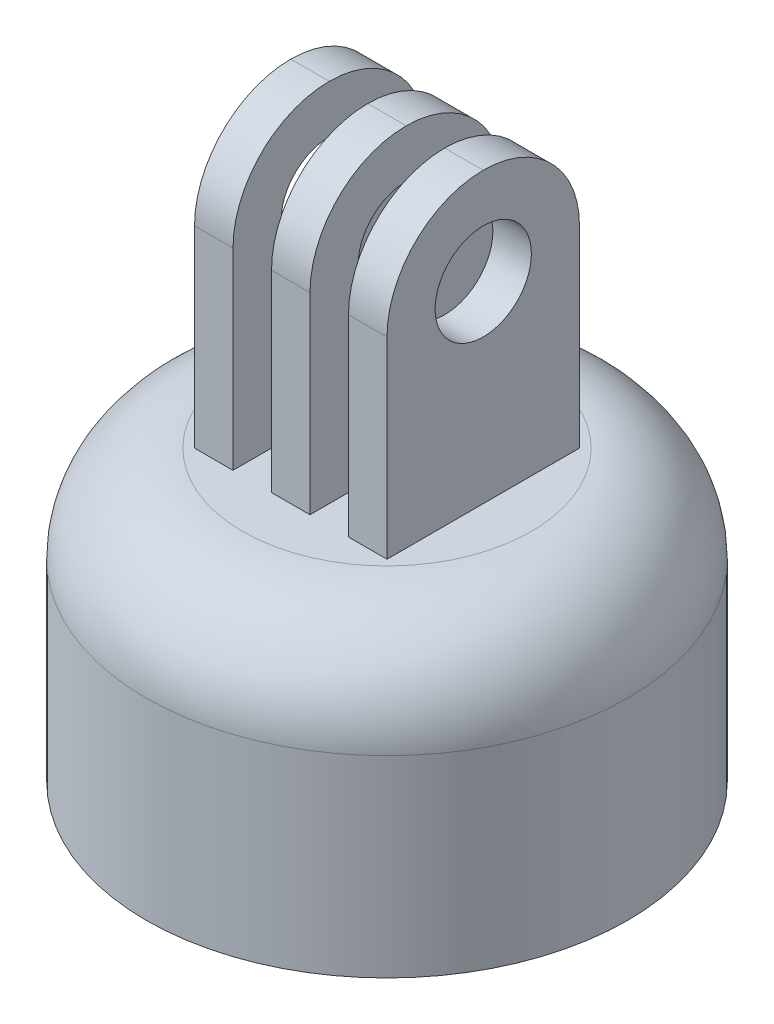
SolidWorks part; units mm, degrees
ref_plane "Front Plane" through (0, 0, 0) normal (0, 0, 1) x (1, 0, 0)
ref_plane "Top Plane" through (0, 0, 0) normal (0, 1, 0) x (1, 0, 0)
ref_plane "Right Plane" through (0, 0, 0) normal (1, 0, 0) x (0, 0, -1)
sketch "Sketch1" plane through (0, 0, 0) normal (0, 1, 0) x (1, 0, 0)
  circle A0 centre (0, 0) radius 10.5
  circle A1 centre (0, 0) radius 12.5
  dimension "D1" = 25
  dimension "D2" = 21
extrude "Boss-Extrude1" add sketch "Sketch1" along normal blind 10
sketch "Sketch2" plane through (0, 10, 0) normal (0, 1, 0) x (1, 0, 0)
  circle A1 centre (0, 0) radius 12.5
  circle A2 centre (0, 0) radius 12.5
  dimension "D1" = 0
extrude "Boss-Extrude2" add sketch "Sketch2" along normal blind 5
sketch "Sketch3" plane through (0, 15, 0) normal (0, 1, 0) x (1, 0, 0)
  line L0 (5, -5) -> (3, -5)
  line L1 (1, -5) -> (-1, -5)
  line L2 (1, -5) -> (1, 5)
  line L3 (1, 5) -> (-1, 5)
  line L4 (-1, -5) -> (-1, 5)
  line L5 (1, -5) -> (-1, 5) construction
  line L6 (1, 5) -> (-1, -5) construction
  line L7 (5, -5) -> (5, 5)
  line L8 (5, 5) -> (3, 5)
  line L9 (3, -5) -> (3, 5)
  line L10 (5, -5) -> (3, 5) construction
  line L11 (5, 5) -> (3, -5) construction
  line L12 (-3, -5) -> (-5, -5)
  line L13 (-3, -5) -> (-3, 5)
  line L14 (-3, 5) -> (-5, 5)
  line L15 (-5, -5) -> (-5, 5)
  line L16 (-3, -5) -> (-5, 5) construction
  line L17 (-3, 5) -> (-5, -5) construction
  point P0 (0, 0)
  point P7 (4, 0)
  point P12 (-4, 0)
  dimension "D1" = 2
  dimension "D2" = 10
  dimension "D3" = 2
  dimension "D4" = 2
extrude "Boss-Extrude3" add sketch "Sketch3" along normal blind 15
fillet "Fillet1" radius 5 1 edges at (0, 15, 12.5)
fillet "Fillet2" radius 5 6 edges at (-4, 30, -5) (0, 30, -5) (4, 30, -5) (-4, 30, 5) (0, 30, 5) (4, 30, 5)
sketch "Sketch4" plane through (5, 0, 0) normal (1, 0, 0) x (0, 0, -1)
  circle A0 centre (0, 25) radius 2.5
  dimension "D1" = 5
extrude "Cut-Extrude1" cut sketch "Sketch4" against normal blind 15
